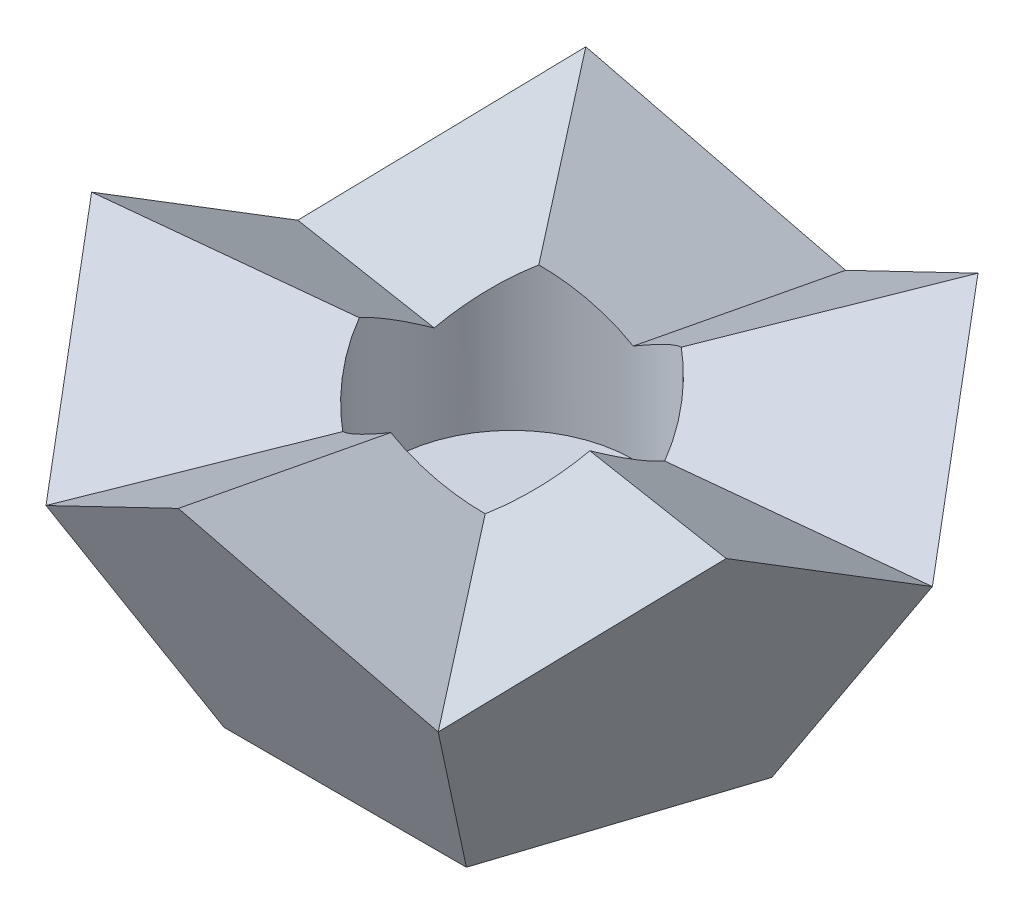
SolidWorks part; units mm, degrees
ref_plane "Front Plane" through (0, 0, 0) normal (0, 0, 1) x (1, 0, 0)
ref_plane "Top Plane" through (0, 0, 0) normal (0, 1, 0) x (1, 0, 0)
ref_plane "Right Plane" through (0, 0, 0) normal (1, 0, 0) x (0, 0, -1)
ref_axis "Axis1" through (0, 18.3541, 0) along (0, -1, 0)
sketch "Sketch2" plane through (0, 0, 0) normal (0, 1, 0) x (1, 0, 0)
  line L1 (0, 5.4016) -> (-5.1373, 1.6692)
  line L2 (-5.1373, 1.6692) -> (-3.175, -4.37)
  line L3 (-3.175, -4.37) -> (3.175, -4.37)
  line L4 (3.175, -4.37) -> (5.1373, 1.6692)
  line L5 (5.1373, 1.6692) -> (0, 5.4016)
  circle A0 centre (0, 0) radius 4.37 construction
  dimension "D1" = 6.35
extrude "Boss-Extrude1" add sketch "Sketch2" along normal blind 6.35 draft 31.717
mirror "Mirror1" about plane through (5.1373, 0, -1.6692) normal (0.5, 0.5257, -0.6882) of "Boss-Extrude1"
mirror "Mirror3" about plane through (-5.1373, 0, -1.6692) normal (-0.809, 0.5257, 0.2629) of "Boss-Extrude1"
mirror "Mirror4" about plane through (0, 0, -5.4016) normal (-0.5, 0.5257, -0.6882) of "Boss-Extrude1"
mirror "Mirror5" about plane through (-3.175, 0, 4.37) normal (0, 0.5257, 0.8507) of "Boss-Extrude1"
mirror "Mirror6" about plane through (3.175, 0, 4.37) normal (0.809, 0.5257, 0.2629) of "Boss-Extrude1"
sketch "Sketch3" plane through (-3.0074, 5.1165, -0.9772) normal (-0.5, 0.8507, -0.1625) x (0.866, 0.4911, -0.0938)
  line L0 (3.4727, -0.4193) -> (4.0774, -0.6503) construction
  point P0 (3.775, -0.5348)
ref_plane "Plane1" through (0.2619, 7.0708, -0.8059) normal (0, -1, 0) x (-1, 0, 0)
sketch "Sketch4" plane through (0.2619, 7.0708, -0.8059) normal (0, -1, 0) x (-1, 0, 0)
  circle A0 centre (0.2619, -0.8059) radius 3.175
  dimension "D1" = 6.35
extrude "Cut-Extrude1" cut sketch "Sketch4" against normal through all and the other way blind 3.175
equation "\"angle between faces\"= arccos ( - sqr ( 5 ) / 5 )"
equation "\"edges per side\"= 5"
equation "\"edge\"= .25"
equation "\"D1@Sketch2\"=\"edge\""
equation "\"D3@Boss-Extrude1\"=(180-\"angle between faces\")/2"
equation "\"D1@Boss-Extrude1\"=\"edge\""
